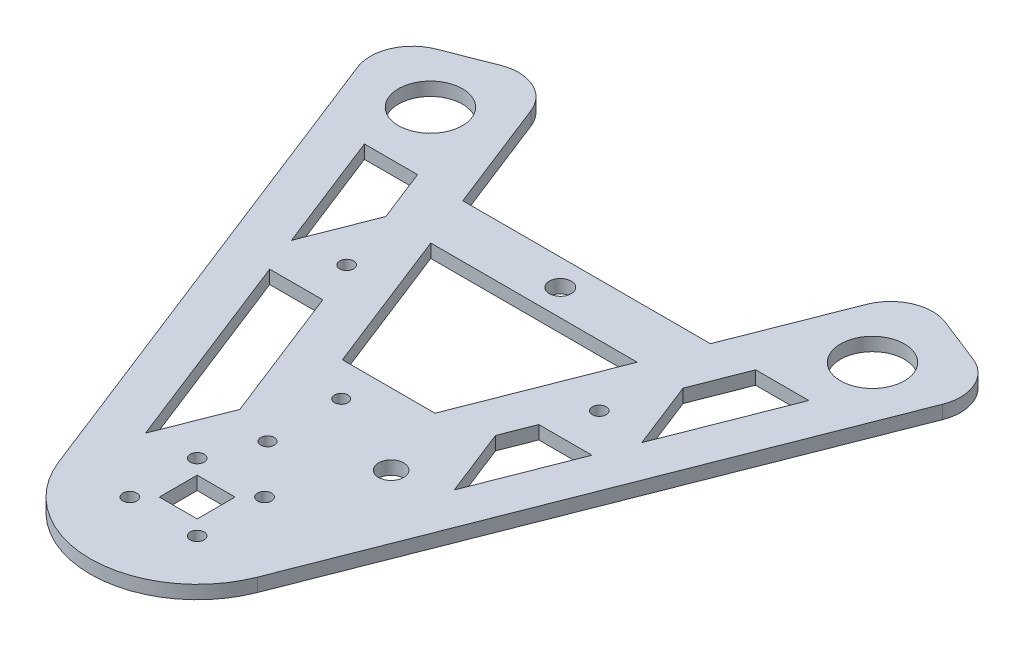
SolidWorks part; units mm, degrees
ref_plane "Front Plane" through (0, 0, 0) normal (0, 0, 1) x (1, 0, 0)
ref_plane "Top Plane" through (0, 0, 0) normal (0, 1, 0) x (1, 0, 0)
ref_plane "Right Plane" through (0, 0, 0) normal (1, 0, 0) x (0, 0, -1)
sketch "Sketch1" plane through (0, 0, 0) normal (0, 1, 0) x (1, 0, 0)
  line L0 (-52.5, 107.9062) -> (52.5, 107.9062) construction
  line L1 (-4.5, -4.5) -> (4.5, -4.5)
  line L2 (-4.5, -4.5) -> (-4.5, 4.5)
  line L3 (-4.5, 4.5) -> (4.5, 4.5)
  line L4 (4.5, -4.5) -> (4.5, 4.5)
  line L5 (-4.5, -4.5) -> (4.5, 4.5) construction
  line L6 (-4.5, 4.5) -> (4.5, -4.5) construction
  line L7 (-73.0716, 116.8972) -> (-23.6501, -9.2645)
  line L8 (23.6501, -9.2645) -> (73.0716, 116.8972)
  line L9 (-43.509, 128.4779) -> (0, 17.4095)
  line L10 (0, 17.4095) -> (43.509, 128.4779)
  line L11 (43.509, 128.4779) -> (73.0716, 116.8972)
  line L12 (-73.0716, 116.8972) -> (-43.509, 128.4779)
  line L13 (-51.2194, 104.6372) -> (-33.5576, 59.5507) construction
  line L14 (-5.0565, -39.0222) -> (18232.1511, 46516.367) construction
  line L15 (-11, 45.4899) -> (11, 45.4899)
  line L16 (17.5, 28.5638) -> (-3.1, 28.5638) construction
  line L17 (-8, -8) -> (8, -8) construction
  line L18 (-8, -8) -> (-8, 8) construction
  line L19 (-8, 8) -> (8, 8) construction
  line L20 (8, -8) -> (8, 8) construction
  line L21 (-8, -8) -> (8, 8) construction
  line L22 (-8, 8) -> (8, -8) construction
  line L23 (-3.1, 37.3138) -> (-3.1, 19.8138) construction
  line L24 (-30, 65.5063) -> (30, 65.5063) construction
  line L25 (-29.4153, 92.5) -> (29.4153, 92.5)
  line L26 (-24.5187, 80) -> (24.5187, 80)
  line L27 (0, 80) -> (0, 92.5) construction
  circle A0 centre (52.5, 107.9062) radius 7.6
  circle A1 centre (-52.5, 107.9062) radius 7.6
  arc A2 (23.6501, -9.2645) -> (-23.6501, -9.2645) centre (0, 0) cw
  circle A6 centre (-30, 65.5063) radius 1.65
  circle A7 centre (30, 65.5063) radius 1.65
  circle A8 centre (17.5, 28.5638) radius 3
  circle A9 centre (-8, 8) radius 1.65
  circle A10 centre (8, 8) radius 1.65
  circle A11 centre (8, -8) radius 1.65
  circle A12 centre (-8, -8) radius 1.65
  circle A13 centre (-3.1, 37.3138) radius 1.6
  circle A14 centre (-3.1, 19.8138) radius 1.6
  circle A15 centre (0, 86.25) radius 2.6
  point P4 (0, 0)
  point P10 (0, 107.9062)
  point P19 (58.2903, 122.6875)
  point P20 (-58.2903, 122.6875)
  point P45 (0, 65.5063)
  point P49 (-3.1, 28.5638)
  point P56 (0, 86.25)
  dimension "D3" = 15.2
  dimension "D7" = 25.4
  dimension "D8" = 3.3
  dimension "D9" = 48
  dimension "D11" = 6
  dimension "D14" = 3.3
  dimension "D17" = 3.2
  dimension "D22" = 5.2
  dimension "D1" = 9
  dimension "D2" = 31.75
  dimension "D4" = 120
  dimension "D5" = 105
  dimension "D6" = 15.875
  dimension "D10" = 22
  dimension "D12" = 39
  dimension "D13" = 16
  dimension "D15" = 20.6
  dimension "D16" = 17.5
  dimension "D18" = 60
  dimension "D19" = 17.5
  dimension "D20" = 12.5
  dimension "D21" = 80
extrude "Boss-Extrude1" add sketch "Sketch1" along normal blind 3.175 contours L7 L8 A2 | A2 L8 L11 L10 L9 L12 L7 A7 A6 A1 A0 L4 L1 L2 L3 | L15 L9 L10 A8 | L9 L26 L10 L25 A15 region at (-57.5163, 0, -120.7116) region at (0, 0, -91.8986) region at (0.0829, 0, -36.0981)
fillet "Fillet1" radius 10 4 edges at (73.0716, 1.5875, -116.8972) (43.509, 1.5875, -128.4779) (-43.509, 1.5875, -128.4779) (-73.0716, 1.5875, -116.8972)
sketch "Sketch2" plane through (0, 3.175, 0) normal (0, 1, 0) x (1, 0, 0)
  line L0 (-38.2766, 55.4899) -> (-25.6572, 55.4899)
  line L1 (-25.6572, 55.4899) -> (-12.9719, 23.1072)
  line L2 (-12.9719, 23.1072) -> (-19.2816, 7)
  line L3 (-19.2816, 7) -> (-38.2766, 55.4899)
  line L8 (-52.7746, 92.5) -> (-41.6102, 64)
  line L9 (-41.6102, 64) -> (-35.3006, 80.1072)
  line L10 (-35.3006, 80.1072) -> (-40.1552, 92.5)
  line L11 (-40.1552, 92.5) -> (-52.7746, 92.5)
  line L12 (-69.4242, 107.5862) -> (-23.6501, -9.2645) construction
  line L13 (-28.7791, 31.245) -> (-38.0901, 27.5975) construction
  line L14 (-47.1924, 78.25) -> (-56.5035, 74.6026) construction
  line L15 (-37.7279, 86.3036) -> (-28.4168, 89.951) construction
  line L16 (-19.3145, 39.2986) -> (-10.0035, 42.946) construction
  line L17 (-24.5187, 80) -> (-11, 45.4899) construction
  line L18 (11, 45.4899) -> (24.5187, 80) construction
  line L19 (-24.5187, 80) -> (24.5187, 80) construction
  line L20 (-29.4153, 92.5) -> (29.4153, 92.5) construction
  line L21 (-11, 45.4899) -> (11, 45.4899) construction
  line L22 (25.6572, 55.4899) -> (38.2766, 55.4899)
  line L23 (38.2766, 55.4899) -> (29.0709, 31.9899)
  line L24 (29.0709, 31.9899) -> (22.7612, 48.0971)
  line L25 (22.7612, 48.0971) -> (25.6572, 55.4899)
  line L26 (40.1552, 92.5) -> (52.7746, 92.5)
  line L27 (52.7746, 92.5) -> (41.6102, 64)
  line L28 (41.6102, 64) -> (35.3006, 80.1072)
  line L29 (35.3006, 80.1072) -> (40.1552, 92.5)
  line L30 (23.6501, -9.2645) -> (69.4242, 107.5862) construction
  line L31 (47.1924, 78.25) -> (56.5035, 74.6026) construction
  line L32 (37.7279, 86.3036) -> (28.4168, 89.951) construction
  line L33 (29.4153, 92.5) -> (39.8615, 119.1668) construction
  point P45 (0, 0)
  point P46 (0, 0)
  point P47 (28.4168, 31.245)
  dimension "D1" = 10
  dimension "D2" = 10
  dimension "D3" = 16
  dimension "D4" = 7
  dimension "D5" = 13.5
extrude "Cut-Extrude1" cut sketch "Sketch2" against normal through all both and the other way through all
